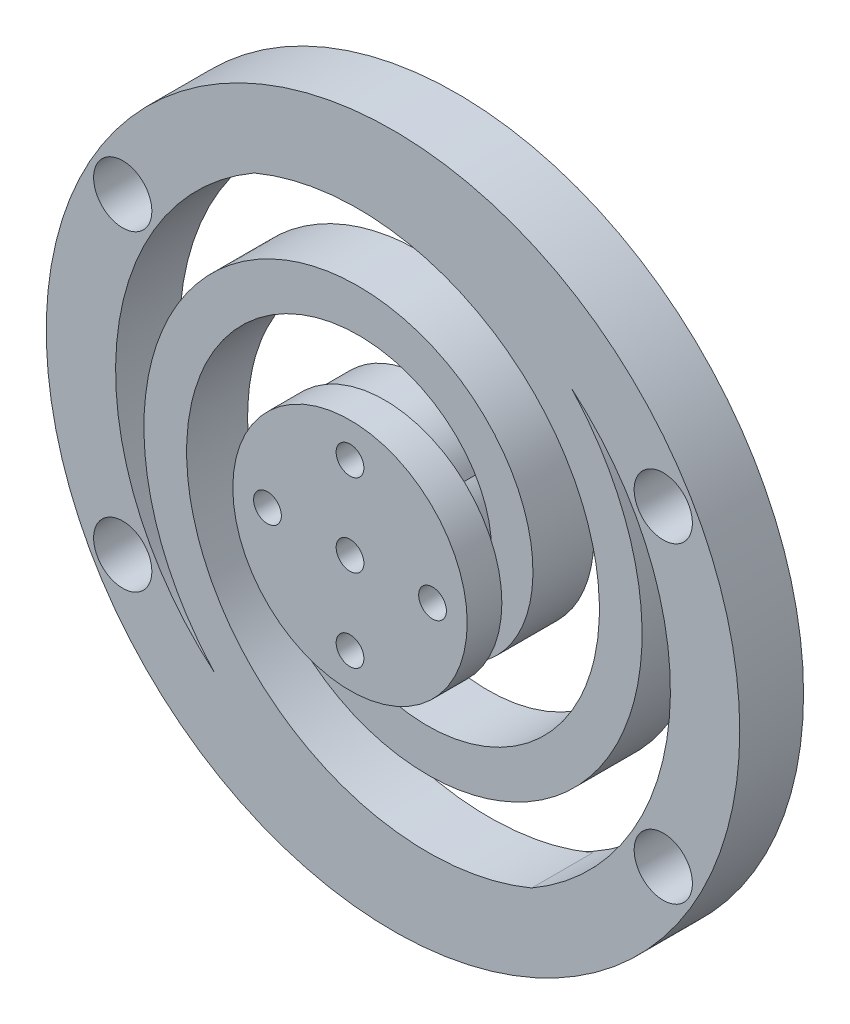
SolidWorks part; units mm, degrees
ref_plane "정면" through (0, 0, 0) normal (0, 0, 1) x (1, 0, 0)
ref_plane "윗면" through (0, 0, 0) normal (0, 1, 0) x (1, 0, 0)
ref_plane "우측면" through (0, 0, 0) normal (1, 0, 0) x (0, 0, -1)
sketch "스케치2" plane through (0, 0, 0) normal (0, 0, 1) x (1, 0, 0)
  circle A0 centre (0, 0) radius 25
  circle A1 centre (0, 0) radius 20
  point P13 (4.2374, 0.9394)
  dimension "D1" = 50
  dimension "D2" = 40
extrude "보스-돌출2" add sketch "스케치2" along normal blind 4.6
sketch "스케치23" plane through (0, 0, 4.6) normal (0, 0, 1) x (1, 0, 0)
  line L0 (0, 0) -> (19.4856, 11.25) construction
  line L1 (0, 0) -> (0, 25) construction
  line L2 (0, 0) -> (25, 0) construction
  circle A0 centre (19.4856, 11.25) radius 2.1
  circle A1 centre (0, 0) radius 25 construction
  circle A2 centre (-19.4856, 11.25) radius 2.1
  circle A3 centre (19.4856, -11.25) radius 2.1
  circle A4 centre (-19.4856, -11.25) radius 2.1
  dimension "D1" = 4.2
  dimension "D2" = 22.5
  dimension "D3" = 60
extrude "컷-돌출8" cut sketch "스케치23" against normal offset from surface (3.1 mm away) 1.5 up to face at (25, 0, 0)
sketch "스케치24" plane through (0, 0, 1.5) normal (0, 0, 1) x (1, 0, 0)
  circle A0 centre (-19.4856, 11.25) radius 1.2
  circle A1 centre (19.4856, 11.25) radius 1.2
  circle A2 centre (19.4856, -11.25) radius 1.2
  circle A3 centre (-19.4856, -11.25) radius 1.2
  dimension "D1" = 2.4
extrude "컷-돌출9" cut sketch "스케치24" against normal through all
sketch "스케치3" plane through (0, 0, 4.6) normal (0, 0, 1) x (1, 0, 0)
  circle A0 centre (0, 0) radius 10
  dimension "D1" = 20
curve "나선형 곡선1"
sketch "스케치4" plane through (0, 0, 4.6) normal (0, 0, 1) x (1, 0, 0)
  circle A0 centre (0, 0) radius 10
  dimension "D1" = 20
curve "나선형 곡선2"
sketch "스케치5" plane through (0, 0, 4.6) normal (0, 0, 1) x (1, 0, 0)
  circle A0 centre (0, 0) radius 10
  dimension "D1" = 20
curve "나선형 곡선3"
sketch "스케치6" plane through (0, 0, 4.6) normal (0, 0, 1) x (1, 0, 0)
  circle A0 centre (0, 0) radius 10
  dimension "D1" = 20
curve "나선형 곡선4"
sketch "스케치30" plane through (0, 0, 4.6) normal (0, 0, 1) x (1, 0, 0)
  circle A0 centre (0, 0) radius 20
curve "나선형 곡선5"
sketch "스케치31" plane through (0, 0, 4.6) normal (0, 0, 1) x (1, 0, 0)
  circle A0 centre (0, 0) radius 20
curve "나선형 곡선6"
sketch "스케치32" plane through (0, 0, 4.6) normal (0, 0, 1) x (1, 0, 0)
  circle A0 centre (0, 0) radius 20
curve "나선형 곡선7"
sketch "스케치33" plane through (0, 0, 4.6) normal (0, 0, 1) x (1, 0, 0)
  circle A0 centre (0, 0) radius 20
curve "나선형 곡선8"
sketch "스케치8" plane through (0, 0, 4.6) normal (0, 0, 1) x (1, 0, 0)
  arc A0 (-2, 3.4641) -> (-2.5712, -3.0642) centre (0, 0) ccw
  arc A1 (2, -3.4641) -> (2.5712, 3.0642) centre (0, 0) ccw
  arc A2 (-12.8558, -15.3209) -> (10, -17.3205) centre (0, 0) ccw
  arc A3 (12.8558, 15.3209) -> (-10, 17.3205) centre (0, 0) ccw
  spline S4 degree 3 poles (-87.6539, 1972.12) (252.3065, -10.6222) (13.0056, -58.5902) (-15.8766, -11.1058) (-16.4268, -9.9532) (-17.2796, -7.5932) (-17.5821, -6.3859) (-17.9397, -3.9677) (-17.9949, -2.7569) (-17.8682, -0.3807) (-17.6864, 0.7848) (-17.1056, 3.0256) (-16.7067, 4.101) (-15.7197, 6.123) (-15.1315, 7.0697) (-13.8004, 8.8029) (-13.0575, 9.5895) (-11.4559, 10.9797) (-10.5973, 11.5832) (-8.8063, 12.5932) (-7.874, 12.9997) (-5.9785, 13.6106) (-5.0153, 13.8152) (-3.0998, 14.0263) (-2.1475, 14.0329) (-0.2928, 13.8606) (0.6095, 13.6816) (2.3299, 13.1579) (3.1478, 12.8131) (5.4319, 11.5687) (6.7244, 10.4576) (8.7025, 7.9275) (9.3879, 6.5104) (10.1263, 3.6481) (10.1799, 2.2046) (9.744, -0.4615) (9.2556, -1.683) (7.9113, -3.7297) (7.0568, -4.5544) (5.1999, -5.7302) (4.1989, -6.0816) (2.2656, -6.3365) (1.3344, -6.2408) (-0.2885, -5.7136) (-0.9796, -5.2833) (-16.7729, 10.2311) (109.9136, 95.7694) (448.2867, -1948.9806) knots -1.286898 -1.286898 -1.286898 -1.286898 0.03125 0.03125 0.0625 0.0625 0.09375 0.09375 0.125 0.125 0.15625 0.15625 0.1875 0.1875 0.21875 0.21875 0.25 0.25 0.28125 0.28125 0.3125 0.3125 0.34375 0.34375 0.375 0.375 0.40625 0.40625 0.4375 0.4375 0.5 0.5 0.5625 0.5625 0.625 0.625 0.6875 0.6875 0.75 0.75 0.8125 0.8125 0.875 0.875 0.9375 0.9375 2.758848 2.758848 2.758848 2.758848 only from (-12.8558, -15.3209) to (-2.5712, -3.0642) construction
  spline S5 degree 3 poles (-1883.166, 592.137) (96.2755, 233.4575) (59.5049, -7.8178) (5.006, -18.7176) (3.7347, -18.8404) (1.2253, -18.8345) (-0.0126, -18.7059) (-2.4073, -18.2149) (-3.5639, -17.8526) (-5.7536, -16.9208) (-6.7865, -16.3513) (-8.6936, -15.0392) (-9.5677, -14.2966) (-11.1302, -12.6774) (-11.8186, -11.801) (-12.9921, -9.9574) (-13.4771, -8.9902) (-14.2357, -7.0098) (-14.5091, -5.9965) (-14.8457, -3.9681) (-14.9088, -2.953) (-14.8346, -0.9628) (-14.6973, 0.0123) (-14.2406, 1.8844) (-13.9211, 2.7815) (-13.1248, 4.4654) (-12.6481, 5.2522) (-11.5675, 6.6896) (-10.9638, 7.3403) (-9.0132, 9.061) (-7.527, 9.8956) (-4.473, 10.889) (-2.9069, 11.0484) (0.0353, 10.7634) (1.4101, 10.32) (3.7663, 8.9985) (4.7471, 8.1218) (6.2106, 6.1585) (6.6933, 5.0736) (7.1631, 2.9264) (7.151, 1.8657) (6.7292, -0.0383) (6.3208, -0.8806) (5.2703, -2.2253) (4.6297, -2.7275) (-15.3507, -12.2621) (-52.4011, 136.0401) (1984.7658, -245.3389) knots -1.286898 -1.286898 -1.286898 -1.286898 0.03125 0.03125 0.0625 0.0625 0.09375 0.09375 0.125 0.125 0.15625 0.15625 0.1875 0.1875 0.21875 0.21875 0.25 0.25 0.28125 0.28125 0.3125 0.3125 0.34375 0.34375 0.375 0.375 0.40625 0.40625 0.4375 0.4375 0.5 0.5 0.5625 0.5625 0.625 0.625 0.6875 0.6875 0.75 0.75 0.8125 0.8125 0.875 0.875 0.9375 0.9375 2.758848 2.758848 2.758848 2.758848 only from (10, -17.3205) to (2, -3.4641) construction
  spline S6 degree 3 poles (87.6539, -1972.12) (-252.3065, 10.6222) (-13.0056, 58.5902) (15.8766, 11.1058) (16.4268, 9.9532) (17.2796, 7.5932) (17.5821, 6.3859) (17.9397, 3.9677) (17.9949, 2.7569) (17.8682, 0.3807) (17.6864, -0.7848) (17.1056, -3.0256) (16.7067, -4.101) (15.7197, -6.123) (15.1315, -7.0697) (13.8004, -8.8029) (13.0575, -9.5895) (11.4559, -10.9797) (10.5973, -11.5832) (8.8063, -12.5932) (7.874, -12.9997) (5.9785, -13.6106) (5.0153, -13.8152) (3.0998, -14.0263) (2.1475, -14.0329) (0.2928, -13.8606) (-0.6095, -13.6816) (-2.3299, -13.1579) (-3.1478, -12.8131) (-5.4319, -11.5687) (-6.7244, -10.4576) (-8.7025, -7.9275) (-9.3879, -6.5104) (-10.1263, -3.6481) (-10.1799, -2.2046) (-9.744, 0.4615) (-9.2556, 1.683) (-7.9113, 3.7297) (-7.0568, 4.5544) (-5.1999, 5.7302) (-4.1989, 6.0816) (-2.2656, 6.3365) (-1.3344, 6.2408) (0.2885, 5.7136) (0.9796, 5.2833) (16.7729, -10.2311) (-109.9136, -95.7694) (-448.2867, 1948.9806) knots -1.286898 -1.286898 -1.286898 -1.286898 0.03125 0.03125 0.0625 0.0625 0.09375 0.09375 0.125 0.125 0.15625 0.15625 0.1875 0.1875 0.21875 0.21875 0.25 0.25 0.28125 0.28125 0.3125 0.3125 0.34375 0.34375 0.375 0.375 0.40625 0.40625 0.4375 0.4375 0.5 0.5 0.5625 0.5625 0.625 0.625 0.6875 0.6875 0.75 0.75 0.8125 0.8125 0.875 0.875 0.9375 0.9375 2.758848 2.758848 2.758848 2.758848 only from (12.8558, 15.3209) to (2.5712, 3.0642) construction
  spline S7 degree 3 poles (1883.166, -592.137) (-96.2755, -233.4575) (-59.5049, 7.8178) (-5.006, 18.7176) (-3.7347, 18.8404) (-1.2253, 18.8345) (0.0126, 18.7059) (2.4073, 18.2149) (3.5639, 17.8526) (5.7536, 16.9208) (6.7865, 16.3513) (8.6936, 15.0392) (9.5677, 14.2966) (11.1302, 12.6774) (11.8186, 11.801) (12.9921, 9.9574) (13.4771, 8.9902) (14.2357, 7.0098) (14.5091, 5.9965) (14.8457, 3.9681) (14.9088, 2.953) (14.8346, 0.9628) (14.6973, -0.0123) (14.2406, -1.8844) (13.9211, -2.7815) (13.1248, -4.4654) (12.6481, -5.2522) (11.5675, -6.6896) (10.9638, -7.3403) (9.0132, -9.061) (7.527, -9.8956) (4.473, -10.889) (2.9069, -11.0484) (-0.0353, -10.7634) (-1.4101, -10.32) (-3.7663, -8.9985) (-4.7471, -8.1218) (-6.2106, -6.1585) (-6.6933, -5.0736) (-7.1631, -2.9264) (-7.151, -1.8657) (-6.7292, 0.0383) (-6.3208, 0.8806) (-5.2703, 2.2253) (-4.6297, 2.7275) (15.3507, 12.2621) (52.4011, -136.0401) (-1984.7658, 245.3389) knots -1.286898 -1.286898 -1.286898 -1.286898 0.03125 0.03125 0.0625 0.0625 0.09375 0.09375 0.125 0.125 0.15625 0.15625 0.1875 0.1875 0.21875 0.21875 0.25 0.25 0.28125 0.28125 0.3125 0.3125 0.34375 0.34375 0.375 0.375 0.40625 0.40625 0.4375 0.4375 0.5 0.5 0.5625 0.5625 0.625 0.625 0.6875 0.6875 0.75 0.75 0.8125 0.8125 0.875 0.875 0.9375 0.9375 2.758848 2.758848 2.758848 2.758848 only from (-10, 17.3205) to (-2, 3.4641) construction
  spline S8 degree 3 poles (-12.8558, -15.3209) (-13.7514, -14.3518) (-14.5389, -13.3052) (-15.8766, -11.1058) (-16.4268, -9.9532) (-17.2796, -7.5932) (-17.5821, -6.3859) (-17.9397, -3.9677) (-17.9949, -2.7569) (-17.8682, -0.3807) (-17.6864, 0.7848) (-17.1056, 3.0256) (-16.7067, 4.101) (-15.7197, 6.123) (-15.1315, 7.0697) (-13.8004, 8.8029) (-13.0575, 9.5895) (-11.4559, 10.9797) (-10.5973, 11.5832) (-8.8063, 12.5932) (-7.874, 12.9997) (-5.9785, 13.6106) (-5.0153, 13.8152) (-3.0998, 14.0263) (-2.1475, 14.0329) (-0.2928, 13.8606) (0.6095, 13.6816) (2.3299, 13.1579) (3.1478, 12.8131) (5.4319, 11.5687) (6.7244, 10.4576) (8.7025, 7.9275) (9.3879, 6.5104) (10.1263, 3.6481) (10.1799, 2.2046) (9.744, -0.4615) (9.2556, -1.683) (7.9113, -3.7297) (7.0568, -4.5544) (5.1999, -5.7302) (4.1989, -6.0816) (2.2656, -6.3365) (1.3344, -6.2408) (-0.2885, -5.7136) (-0.9796, -5.2833) (-2.0275, -4.2539) (-2.3843, -3.6561) (-2.5712, -3.0642) knots 0 0 0 0 0.03125 0.03125 0.0625 0.0625 0.09375 0.09375 0.125 0.125 0.15625 0.15625 0.1875 0.1875 0.21875 0.21875 0.25 0.25 0.28125 0.28125 0.3125 0.3125 0.34375 0.34375 0.375 0.375 0.40625 0.40625 0.4375 0.4375 0.5 0.5 0.5625 0.5625 0.625 0.625 0.6875 0.6875 0.75 0.75 0.8125 0.8125 0.875 0.875 0.9375 0.9375 1 1 1 1
  spline S9 degree 3 poles (10, -17.3205) (8.783, -17.8307) (7.5302, -18.2127) (5.006, -18.7176) (3.7347, -18.8404) (1.2253, -18.8345) (-0.0126, -18.7059) (-2.4073, -18.2149) (-3.5639, -17.8526) (-5.7536, -16.9208) (-6.7865, -16.3513) (-8.6936, -15.0392) (-9.5677, -14.2966) (-11.1302, -12.6774) (-11.8186, -11.801) (-12.9921, -9.9574) (-13.4771, -8.9902) (-14.2357, -7.0098) (-14.5091, -5.9965) (-14.8457, -3.9681) (-14.9088, -2.953) (-14.8346, -0.9628) (-14.6973, 0.0123) (-14.2406, 1.8844) (-13.9211, 2.7815) (-13.1248, 4.4654) (-12.6481, 5.2522) (-11.5675, 6.6896) (-10.9638, 7.3403) (-9.0132, 9.061) (-7.527, 9.8956) (-4.473, 10.889) (-2.9069, 11.0484) (0.0353, 10.7634) (1.4101, 10.32) (3.7663, 8.9985) (4.7471, 8.1218) (6.2106, 6.1585) (6.6933, 5.0736) (7.1631, 2.9264) (7.151, 1.8657) (6.7292, -0.0383) (6.3208, -0.8806) (5.2703, -2.2253) (4.6297, -2.7275) (3.3039, -3.3601) (2.6201, -3.491) (2, -3.4641) knots 0 0 0 0 0.03125 0.03125 0.0625 0.0625 0.09375 0.09375 0.125 0.125 0.15625 0.15625 0.1875 0.1875 0.21875 0.21875 0.25 0.25 0.28125 0.28125 0.3125 0.3125 0.34375 0.34375 0.375 0.375 0.40625 0.40625 0.4375 0.4375 0.5 0.5 0.5625 0.5625 0.625 0.625 0.6875 0.6875 0.75 0.75 0.8125 0.8125 0.875 0.875 0.9375 0.9375 1 1 1 1
  spline S10 degree 3 poles (12.8558, 15.3209) (13.7514, 14.3518) (14.5389, 13.3052) (15.8766, 11.1058) (16.4268, 9.9532) (17.2796, 7.5932) (17.5821, 6.3859) (17.9397, 3.9677) (17.9949, 2.7569) (17.8682, 0.3807) (17.6864, -0.7848) (17.1056, -3.0256) (16.7067, -4.101) (15.7197, -6.123) (15.1315, -7.0697) (13.8004, -8.8029) (13.0575, -9.5895) (11.4559, -10.9797) (10.5973, -11.5832) (8.8063, -12.5932) (7.874, -12.9997) (5.9785, -13.6106) (5.0153, -13.8152) (3.0998, -14.0263) (2.1475, -14.0329) (0.2928, -13.8606) (-0.6095, -13.6816) (-2.3299, -13.1579) (-3.1478, -12.8131) (-5.4319, -11.5687) (-6.7244, -10.4576) (-8.7025, -7.9275) (-9.3879, -6.5104) (-10.1263, -3.6481) (-10.1799, -2.2046) (-9.744, 0.4615) (-9.2556, 1.683) (-7.9113, 3.7297) (-7.0568, 4.5544) (-5.1999, 5.7302) (-4.1989, 6.0816) (-2.2656, 6.3365) (-1.3344, 6.2408) (0.2885, 5.7136) (0.9796, 5.2833) (2.0275, 4.2539) (2.3843, 3.6561) (2.5712, 3.0642) knots 0 0 0 0 0.03125 0.03125 0.0625 0.0625 0.09375 0.09375 0.125 0.125 0.15625 0.15625 0.1875 0.1875 0.21875 0.21875 0.25 0.25 0.28125 0.28125 0.3125 0.3125 0.34375 0.34375 0.375 0.375 0.40625 0.40625 0.4375 0.4375 0.5 0.5 0.5625 0.5625 0.625 0.625 0.6875 0.6875 0.75 0.75 0.8125 0.8125 0.875 0.875 0.9375 0.9375 1 1 1 1
  spline S11 degree 3 poles (-10, 17.3205) (-8.783, 17.8307) (-7.5302, 18.2127) (-5.006, 18.7176) (-3.7347, 18.8404) (-1.2253, 18.8345) (0.0126, 18.7059) (2.4073, 18.2149) (3.5639, 17.8526) (5.7536, 16.9208) (6.7865, 16.3513) (8.6936, 15.0392) (9.5677, 14.2966) (11.1302, 12.6774) (11.8186, 11.801) (12.9921, 9.9574) (13.4771, 8.9902) (14.2357, 7.0098) (14.5091, 5.9965) (14.8457, 3.9681) (14.9088, 2.953) (14.8346, 0.9628) (14.6973, -0.0123) (14.2406, -1.8844) (13.9211, -2.7815) (13.1248, -4.4654) (12.6481, -5.2522) (11.5675, -6.6896) (10.9638, -7.3403) (9.0132, -9.061) (7.527, -9.8956) (4.473, -10.889) (2.9069, -11.0484) (-0.0353, -10.7634) (-1.4101, -10.32) (-3.7663, -8.9985) (-4.7471, -8.1218) (-6.2106, -6.1585) (-6.6933, -5.0736) (-7.1631, -2.9264) (-7.151, -1.8657) (-6.7292, 0.0383) (-6.3208, 0.8806) (-5.2703, 2.2253) (-4.6297, 2.7275) (-3.3039, 3.3601) (-2.6201, 3.491) (-2, 3.4641) knots 0 0 0 0 0.03125 0.03125 0.0625 0.0625 0.09375 0.09375 0.125 0.125 0.15625 0.15625 0.1875 0.1875 0.21875 0.21875 0.25 0.25 0.28125 0.28125 0.3125 0.3125 0.34375 0.34375 0.375 0.375 0.40625 0.40625 0.4375 0.4375 0.5 0.5 0.5625 0.5625 0.625 0.625 0.6875 0.6875 0.75 0.75 0.8125 0.8125 0.875 0.875 0.9375 0.9375 1 1 1 1
extrude "보스-돌출3" add sketch "스케치8" against normal blind 4.4
sketch "스케치19" plane through (0, 0, 0.2) normal (0, 0, -1) x (-1, 0, 0)
  circle A0 centre (0, 0) radius 3.975
  dimension "D1" = 7.95
extrude "보스-돌출6" add sketch "스케치19" along normal blind 3.4
sketch "스케치9" plane through (0, 0, -3.2) normal (0, 0, -1) x (-1, 0, 0)
  circle A0 centre (0, 0) radius 3.1
  dimension "D1" = 6.2
extrude "컷-돌출1" cut sketch "스케치9" against normal blind 3.1
sketch "스케치10" plane through (0, 0, 4.6) normal (0, 0, 1) x (1, 0, 0)
  circle A0 centre (0, 0) radius 4
  dimension "D1" = 8
extrude "보스-돌출4" add sketch "스케치10" along normal blind 0.6
sketch "스케치11" plane through (0, 0, 5.2) normal (0, 0, 1) x (1, 0, 0)
  circle A0 centre (0, 0) radius 8.45
  point P14 (0, 0)
  dimension "D1" = 16.9
extrude "보스-돌출5" add sketch "스케치11" along normal blind 2.5
sketch "스케치27" plane through (0, 0, 7.7) normal (0, 0, 1) x (1, 0, 0)
  circle A0 centre (0, 0) radius 5.95 construction
  circle A1 centre (0, 0) radius 8.45 construction
  circle A2 centre (0, 5.95) radius 1
  circle A3 centre (0, -5.95) radius 1
  circle A4 centre (5.95, 0) radius 1
  circle A5 centre (-5.95, 0) radius 1
  dimension "D1" = 2.5
  dimension "D2" = 2
extrude "컷-돌출12" cut sketch "스케치27" against normal up to surface (2.5 mm away) up to face at (4, 0, 5.2)
ref_axis "기준축1" through (0, 0, -3.2) along (0, 0, 1)
fillet "필렛1" [suppressed] radius 0.1
sketch "스케치25" plane through (0, 0, 7.7) normal (0, 0, 1) x (1, 0, 0)
  circle A0 centre (0, 0) radius 1
  dimension "D1" = 2
extrude "컷-돌출10" cut sketch "스케치25" against normal blind 7
